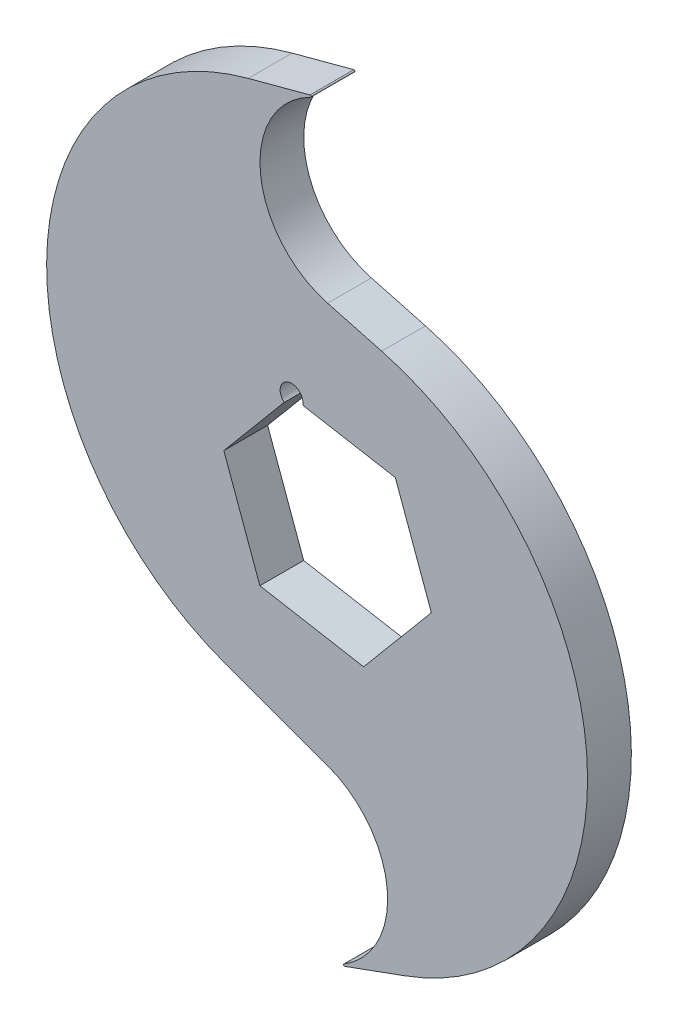
SolidWorks part; units mm, degrees
ref_plane "Front Plane" through (0, 0, 0) normal (0, 0, 1) x (1, 0, 0)
ref_plane "Top Plane" through (0, 0, 0) normal (0, 1, 0) x (1, 0, 0)
ref_plane "Right Plane" through (0, 0, 0) normal (1, 0, 0) x (0, 0, -1)
sketch "Sketch1" plane through (0, 0, 0) normal (0, 0, 1) x (1, 0, 0)
  line L0 (0, 52.07) -> (-11.0405, 49.1117)
  line L1 (0, 52.07) -> (0, 0) construction
  line L2 (0, -52.07) -> (10.7407, -48.1607)
  line L3 (0, 0) -> (0, -52.07) construction
  line L5 (-5.0156, 13.7803) -> (-14.4419, 2.5465)
  line L6 (-14.4419, 2.5465) -> (-9.4263, -11.2338)
  line L7 (-9.4263, -11.2338) -> (5.0156, -13.7803)
  line L8 (5.0156, -13.7803) -> (14.4419, -2.5465)
  line L9 (14.4419, -2.5465) -> (9.4263, 11.2338)
  line L10 (9.4263, 11.2338) -> (-5.0156, 13.7803)
  line L11 (0, 27.5355) -> (7.5237, 25.5195)
  line L12 (0, -28.2018) -> (-14.1906, -23.0368)
  circle A0 centre (0, 0) radius 52.07 construction
  arc A1 (0, 52.07) -> (0, 27.5355) centre (3.287, 39.8027) ccw
  arc A3 (0, -52.07) -> (0, -28.2018) centre (-4.3437, -40.1359) ccw
  arc A4 (10.7407, -48.1607) -> (7.5237, 25.5195) centre (-2.4834, -11.8278) ccw
  arc A5 (-11.0405, 49.1117) -> (-14.1906, -23.0368) centre (-1.2414, 12.5408) ccw
  circle A6 centre (0, 0) radius 12.7 construction
  circle A7 centre (-5.0156, 13.7803) radius 1.5875
  dimension "D4" = 70
  dimension "D5" = 25.4
  dimension "D1" = 104.14
  dimension "D6" = 12.7
  dimension "D8" = 3.175
  dimension "D2" = 11.43
  dimension "D3" = 75
  dimension "D7" = 20
extrude "Boss-Extrude1" add sketch "Sketch1" along normal mid plane 6.096 contours L0 A5 L12 A3 L2 A4 L11 A1 A7 L10 L9 L8 L7 L6 L5 region at (-10.698, 39.8027, 0)
fillet "Fillet1" radius 0.127 2 edges at (0, 52.07, 0) (0, -52.07, 0)
